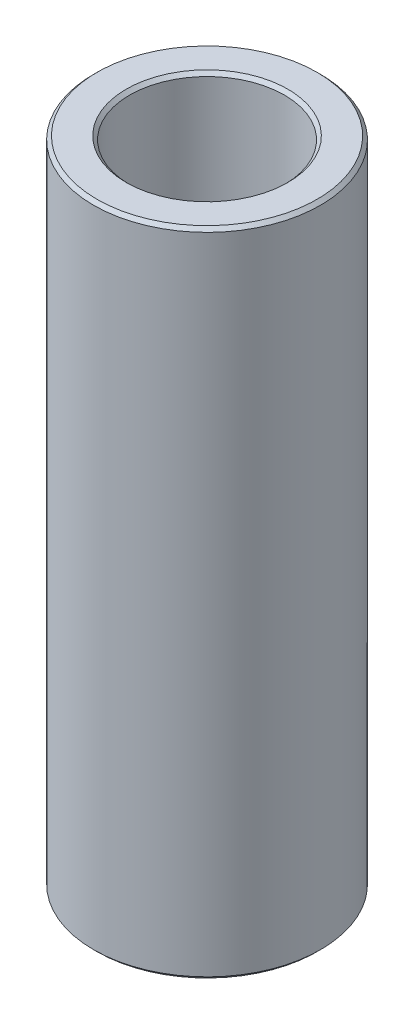
SolidWorks part; units mm, degrees
ref_plane "Front Plane" through (0, 0, 0) normal (0, 0, 1) x (1, 0, 0)
ref_plane "Top Plane" through (0, 0, 0) normal (0, 1, 0) x (1, 0, 0)
ref_plane "Right Plane" through (0, 0, 0) normal (1, 0, 0) x (0, 0, -1)
sketch "Sketch1" plane through (0, 0, 0) normal (0, 1, 0) x (1, 0, 0)
  circle A0 centre (0, 0) radius 50
  dimension "SLEEVE_OD" = 100
extrude "Boss-Extrude1" add sketch "Sketch1" along normal blind 287.1545
sketch "Sketch2" plane through (0, 0, 0) normal (0, 1, 0) x (1, 0, 0)
  circle A0 centre (0, 0) radius 34.1293
  dimension "BORE_D" = 68.2586
extrude "Cut-Extrude1" cut sketch "Sketch2" along normal through all
chamfer "Chamfer1" distance 1.505 angle 45 4 edges at (0, 287.1545, 34.1293) (0, 0, 34.1293) (0, 0, 50) (0, 287.1545, 50)
